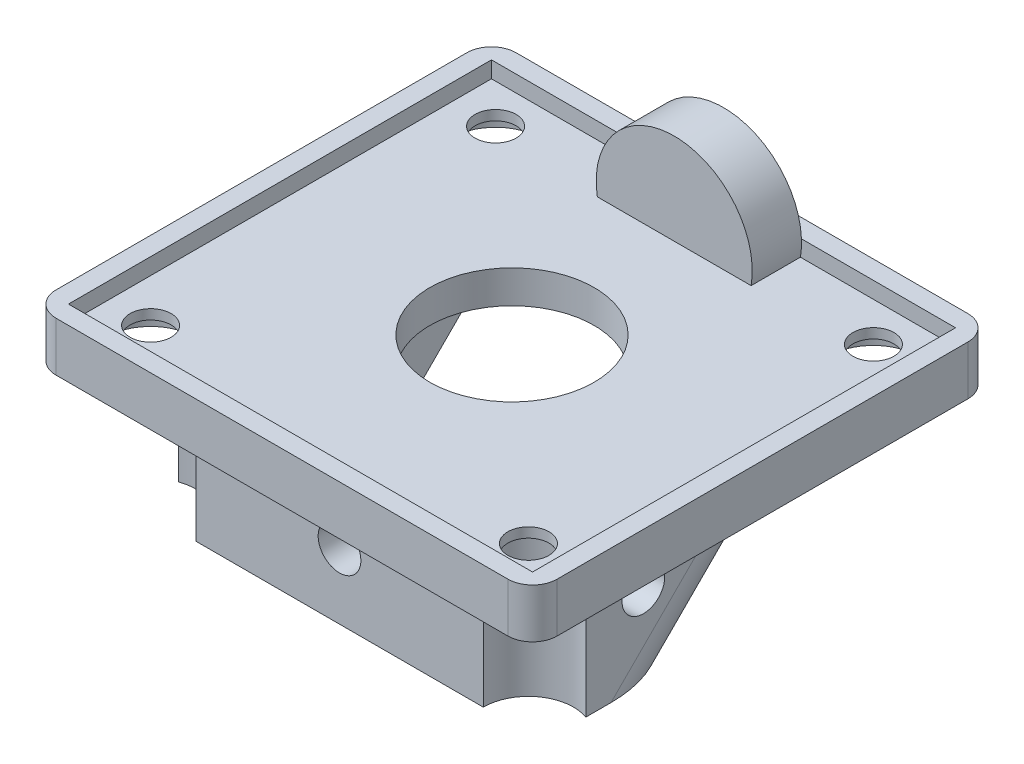
SolidWorks part; units mm, degrees
ref_plane "前视基准面" through (0, 0, 0) normal (0, 0, 1) x (1, 0, 0)
ref_plane "上视基准面" through (0, 0, 0) normal (0, 1, 0) x (1, 0, 0)
ref_plane "右视基准面" through (0, 0, 0) normal (1, 0, 0) x (0, 0, -1)
other "Configuration Table"
sketch "草图1" plane through (0, 0, 0) normal (0, 1, 0) x (1, 0, 0)
  line L1 (0, 0) -> (30.5, 0)
  line L2 (0, 0) -> (0, 28)
  line L3 (0, 28) -> (30.5, 28)
  line L4 (30.5, 0) -> (30.5, 28)
  line L5 (0, 0) -> (30.5, 28) construction
  line L6 (0, 28) -> (30.5, 0) construction
  point P4 (15.25, 14)
  dimension "D1" = 28
  dimension "D2" = 30.5
extrude "凸台-拉伸1" add sketch "草图1" along normal blind 1.6
sketch "草图2" plane through (0, 1.6, 0) normal (0, 1, 0) x (1, 0, 0)
  line L0 (0, 14) -> (30.5, 14) construction
  line L1 (1.125, 26.875) -> (29.375, 26.875)
  line L2 (1.125, 26.875) -> (1.125, 1.125)
  line L3 (1.125, 1.125) -> (29.375, 1.125)
  line L4 (29.375, 26.875) -> (29.375, 1.125)
  line L5 (1.125, 26.875) -> (29.375, 1.125) construction
  line L6 (1.125, 1.125) -> (29.375, 26.875) construction
  line L7 (0, 28) -> (0, 0) construction
  line L8 (30.5, 0) -> (30.5, 28) construction
  line L9 (15.25, 28) -> (15.25, 0) construction
  line L10 (30.5, 28) -> (0, 28) construction
  line L11 (0, 0) -> (30.5, 0) construction
  point P4 (15.25, 14)
  dimension "D1" = 28.25
  dimension "D2" = 25.75
extrude "切除-拉伸1" cut sketch "草图2" against normal blind 1
sketch "草图3" plane through (57.75, 0, -26.875) normal (0, 0, 1) x (1, 0, 0)
  line L0 (-42.5, 1.4) -> (-42.5, 0.6) construction
  line L4 (-56.625, 0.6) -> (-28.375, 0.6) construction
  line L5 (-28.375, 1.6) -> (-56.625, 1.6) construction
  line L6 (-47.1821, 0.6) -> (-37.8179, 0.6)
  line L7 (-28.375, 0.6) -> (-56.625, 0.6) construction
  arc A1 (-37.8179, 0.6) -> (-47.1821, 0.6) centre (-42.5, 1.4) ccw
  dimension "D1" = 0.2
  dimension "D2" = 9.5
extrude "凸台-拉伸2" add sketch "草图3" along normal blind 3
sketch "草图5" plane through (0, 0.6, 0) normal (0, 1, 0) x (1, 0, 0)
  line L0 (1.125, 14) -> (29.375, 14) construction
  line L1 (3.75, 24.5) -> (26.75, 24.5) construction
  line L2 (3.75, 24.5) -> (3.75, 3.5) construction
  line L3 (3.75, 3.5) -> (26.75, 3.5) construction
  line L4 (26.75, 24.5) -> (26.75, 3.5) construction
  line L5 (3.75, 24.5) -> (26.75, 3.5) construction
  line L6 (3.75, 3.5) -> (26.75, 24.5) construction
  line L7 (1.125, 26.875) -> (1.125, 1.125) construction
  line L8 (29.375, 1.125) -> (29.375, 26.875) construction
  circle A0 centre (3.75, 24.5) radius 1.25
  circle A1 centre (26.75, 24.5) radius 1.25
  circle A2 centre (3.75, 3.5) radius 1.25
  circle A3 centre (26.75, 3.5) radius 1.25
  point P4 (15.25, 14)
  dimension "D3" = 2.5
  dimension "D1" = 23
  dimension "D2" = 21
extrude "切除-拉伸2" cut sketch "草图5" against normal up to next
sketch "草图6" plane through (0, 0.6, 0) normal (0, 1, 0) x (1, 0, 0)
  line L0 (1.125, 26.875) -> (29.375, 1.125) construction
  line L1 (1.125, 1.125) -> (29.375, 1.125) construction
  circle A0 centre (15.25, 14) radius 5
  dimension "D1" = 10
extrude "切除-拉伸3" cut sketch "草图6" against normal up to next
sketch "草图7" plane through (0, 0, 0) normal (0, -1, 0) x (1, 0, 0)
  line L8 (0, 0) -> (0, -28)
  line L9 (0, -28) -> (30.5, -28)
  line L10 (30.5, -28) -> (30.5, 0)
  line L11 (30.5, 0) -> (0, 0)
  line L12 (0, 0) -> (0, -28)
  line L13 (0, -28) -> (30.5, -28)
  line L14 (30.5, -28) -> (30.5, 0)
  line L15 (30.5, 0) -> (0, 0)
  circle A0 centre (3.75, -3.5) radius 2.75
  circle A1 centre (26.75, -3.5) radius 2.75
  circle A2 centre (3.75, -24.5) radius 2.75
  circle A3 centre (26.75, -24.5) radius 2.75
  circle A4 centre (15.25, -14) radius 5 construction
  circle A5 centre (15.25, -14) radius 5
  dimension "D2" = 5.5
  dimension "D1" = 0
extrude "凸台-拉伸3" add sketch "草图7" along normal blind 1.4
sketch "草图8" plane through (0, -1.4, 0) normal (0, -1, 0) x (1, 0, 0)
  line L0 (22.65, -7) -> (27.65, -7)
  line L1 (2.85, -7) -> (7.85, -7)
  line L2 (2.85, -7) -> (2.85, -21)
  line L3 (2.85, -21) -> (7.85, -21)
  line L4 (27.65, -7) -> (27.65, -21)
  line L5 (2.85, -7) -> (15.25, -14) construction
  line L6 (2.85, -21) -> (15.25, -14) construction
  line L8 (7.85, -7) -> (7.85, -21)
  line L10 (22.65, -7) -> (22.65, -21)
  line L11 (7.85, -7) -> (15.25, -14) construction
  line L12 (7.85, -21) -> (15.25, -14) construction
  line L13 (22.65, -9.8226) -> (27.65, -7) construction
  line L14 (22.65, -18.1774) -> (27.65, -21) construction
  line L15 (22.65, -21) -> (27.65, -21)
  line L16 (15.25, -14) -> (15.25, -9) construction
  circle A0 centre (15.25, -14) radius 5 construction
  point P4 (15.25, -14)
  point P12 (15.25, -14)
  dimension "D1" = 24.8
  dimension "D2" = 14
  dimension "D3" = 5
extrude "凸台-拉伸4" add sketch "草图8" along normal blind 10
sketch "草图9" plane through (2.85, 0, 0) normal (-1, 0, 0) x (0, 0, 1)
  line L0 (-21, -1.4) -> (-11, -11.4)
  line L1 (-21, -11.4) -> (-21, -1.4) construction
  line L2 (-7, -11.4) -> (-21, -11.4) construction
  line L3 (-11, -11.4) -> (-21, -11.4)
  line L4 (-21, -11.4) -> (-21, -1.4)
  dimension "D1" = 10
extrude "切除-拉伸4" cut sketch "草图9" against normal through all
sketch "草图10" plane through (0, 0, -7) normal (0, 0, 1) x (1, 0, 0)
  line L1 (2.85, -11.4) -> (27.65, -11.4)
  line L2 (2.85, -11.4) -> (2.85, -1.4)
  line L3 (2.85, -1.4) -> (27.65, -1.4)
  line L4 (27.65, -11.4) -> (27.65, -1.4)
  line L5 (2.85, -11.4) -> (27.65, -1.4) construction
  line L6 (2.85, -1.4) -> (27.65, -11.4) construction
  point P4 (15.25, -6.4)
extrude "凸台-拉伸5" add sketch "草图10" along normal blind 3.5
sketch "草图11" plane through (0, 0, 0) normal (0, -1, 0) x (1, 0, 0)
  circle A0 centre (3.75, -3.5) radius 2.75 construction
  circle A1 centre (26.75, -3.5) radius 2.75
  circle A2 centre (26.75, -3.5) radius 2.75
  circle A3 centre (3.75, -3.5) radius 2.75
  dimension "D1" = 0
extrude "切除-拉伸5" cut sketch "草图11" along normal through all
sketch "草图12" plane through (2.85, 0, 0) normal (-1, 0, 0) x (0, 0, 1)
  line L0 (0, -1.4) -> (-28, -1.4) construction
  line L2 (-11, -11.4) -> (-21, -1.4) construction
  line L3 (-6.0986, -1.4) -> (-6.0986, -11.4) construction
  circle A0 centre (-9.5986, -4.4) radius 1.3
  dimension "D1" = 2.6
  dimension "D2" = 3
  dimension "D3" = 3.5
  dimension "D4" = 5.9407
extrude "切除-拉伸6" cut sketch "草图12" against normal through all
sketch "草图13" plane through (0, 0, -3.5) normal (0, 0, 1) x (1, 0, 0)
  line L0 (15.25, -11.4) -> (15.25, -1.4) construction
  line L1 (6.5, -11.4) -> (24, -11.4) construction
  line L2 (30.5, -1.4) -> (0, -1.4) construction
  circle A0 centre (15.25, -5.4) radius 1.3
  dimension "D1" = 4
  dimension "D2" = 2.6
extrude "切除-拉伸7" cut sketch "草图13" against normal up to next
sketch "草图14" plane through (27.65, 0, 0) normal (1, 0, 0) x (0, 0, -1)
  line L0 (11, -11.4) -> (21, -1.4) construction
  line L1 (3.5, -11.4) -> (13, -11.4)
  line L2 (3.5, -11.4) -> (3.5, -9.4)
  line L3 (3.5, -9.4) -> (13, -9.4)
  line L4 (13, -11.4) -> (13, -9.4)
  line L5 (3.5, -11.4) -> (13, -9.4) construction
  line L6 (3.5, -9.4) -> (13, -11.4) construction
  circle A0 centre (9.5986, -4.4) radius 1.3 construction
  point P4 (8.25, -10.4)
  dimension "D1" = 5
extrude "切除-拉伸8" cut sketch "草图14" against normal up to next
sketch "草图15" plane through (0, 0, -7) normal (0, 0, -1) x (-1, 0, 0)
  line L4 (-22.65, -9.4) -> (-7.85, -9.4)
  line L5 (-7.85, -9.4) -> (-7.85, -1.4)
  line L6 (-7.85, -1.4) -> (-22.65, -1.4)
  line L7 (-22.65, -1.4) -> (-22.65, -9.4)
  line L8 (-22.65, -9.4) -> (-7.85, -9.4)
  line L9 (-7.85, -9.4) -> (-7.85, -1.4)
  line L10 (-7.85, -1.4) -> (-22.65, -1.4)
  line L11 (-22.65, -1.4) -> (-22.65, -9.4)
  circle A0 centre (-15.25, -5.4) radius 1.3 construction
  circle A1 centre (-15.25, -5.4) radius 1.3
  dimension "D1" = 0
extrude "凸台-拉伸6" add sketch "草图15" along normal blind 2
fillet "圆角1" radius 3.8 2 edges at (27.65, -5.4, -17) (2.85, -5.4, -17)
fillet "圆角2" radius 1.5 4 edges at (0, 0.1, -28) (0, 0.1, 0) (30.5, 0.1, -28) (30.5, 0.1, 0)
fillet "圆角3" radius 3 2 edges at (22.65, -2.323, -9) (7.85, -2.323, -9)
sketch "草图16" plane through (22.65, 0, 0) normal (1, 0, 0) x (0, 0, -1)
  line L1 (9, -5.554) -> (9, -3.246)
  line L2 (9, -5.554) -> (9, -3.246)
  arc A1 (9, -3.246) -> (9, -5.554) centre (9.5986, -4.4) ccw
  arc A2 (9, -3.246) -> (9, -5.554) centre (9.5986, -4.4) ccw
  dimension "D1" = 0
extrude "切除-拉伸9" cut sketch "草图16" against normal up to vertex (3 mm away) up to point (19.65, -3.246, -9)
sketch "草图17" plane through (7.85, 0, 0) normal (-1, 0, 0) x (0, 0, 1)
  line L1 (-9, -3.246) -> (-9, -5.554)
  line L2 (-9, -3.246) -> (-9, -5.554)
  arc A1 (-9, -5.554) -> (-9, -3.246) centre (-9.5986, -4.4) ccw
  arc A2 (-9, -5.554) -> (-9, -3.246) centre (-9.5986, -4.4) ccw
  dimension "D1" = 0
extrude "切除-拉伸10" cut sketch "草图17" against normal up to vertex (3 mm away) up to point (10.85, -3.246, -9)
fillet "圆角4" radius 1 2 edges at (10.85, -4.4, -8.2986) (19.65, -4.4, -8.2986)
